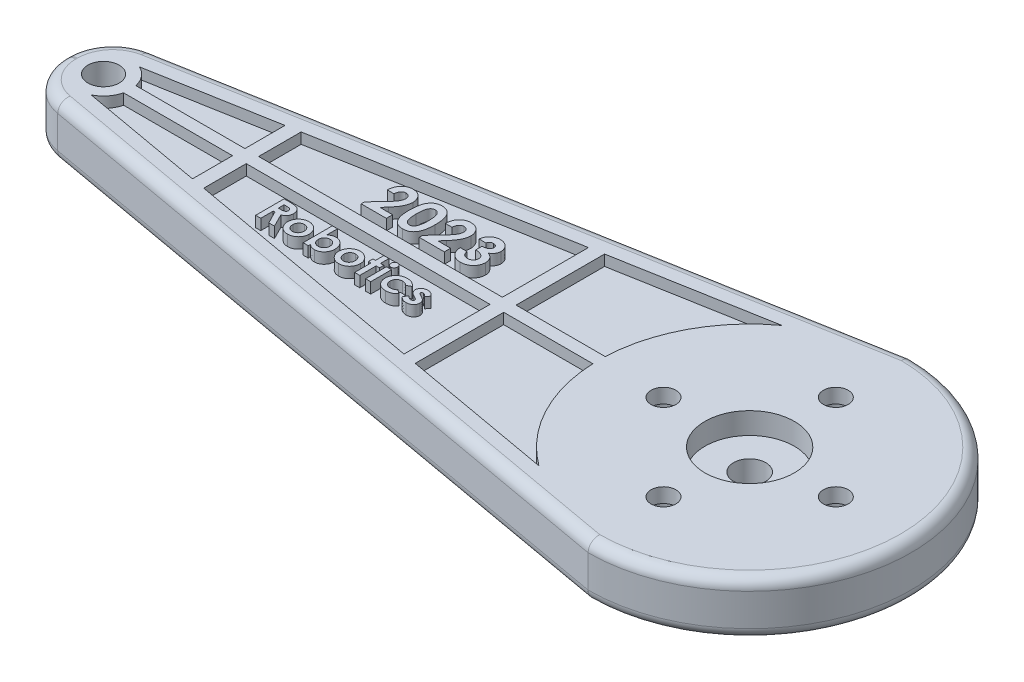
SolidWorks part; units mm, degrees
ref_plane "Front Plane" through (0, 0, 0) normal (0, 0, 1) x (1, 0, 0)
ref_plane "Top Plane" through (0, 0, 0) normal (0, 1, 0) x (1, 0, 0)
ref_plane "Right Plane" through (0, 0, 0) normal (1, 0, 0) x (0, 0, -1)
sketch "Sketch1" plane through (0, 0, 0) normal (0, 1, 0) x (1, 0, 0)
  line L1 (0, 0) -> (-63.5, 0)
  line L2 (0, 0) -> (0, 30)
  line L3 (0, 30) -> (-63.5, 30)
  line L4 (-63.5, 0) -> (-63.5, 30)
  dimension "D1" = 30
  dimension "D2" = 63.5
extrude "Boss-Extrude1" add sketch "Sketch1" along normal blind 5
sketch "Sketch2" plane through (0, 5, 0) normal (0, 1, 0) x (1, 0, 0)
  line L0 (0, 0) -> (0, 30) construction
  circle A0 centre (0, 15) radius 15
extrude "Boss-Extrude3" add sketch "Sketch2" against normal up to surface (5 mm away) up to face at (-31.75, 0, -15)
sketch "Sketch3" plane through (0, 5, 0) normal (0, 1, 0) x (1, 0, 0)
  circle A0 centre (0, 15) radius 1.5
  dimension "D1" = 3
extrude "Cut-Extrude1" cut sketch "Sketch3" against normal blind 5
sketch "Sketch5" plane through (0, 5, 0) normal (0, 1, 0) x (1, 0, 0)
  circle A0 centre (0, 15) radius 4.15
  dimension "D1" = 8.3
extrude "Cut-Extrude3" cut sketch "Sketch5" against normal blind 2
sketch "Sketch6" plane through (0, 0, 0) normal (0, -1, 0) x (1, 0, 0)
  circle A0 centre (0, -15) radius 8.001 construction
  circle A1 centre (0, -6.999) radius 1.15
  circle A2 centre (-8.001, -15) radius 1.15
  circle A3 centre (0, -23.001) radius 1.15
  circle A4 centre (8.001, -15) radius 1.15
  dimension "D1" = 16.002
  dimension "D2" = 2.3
  dimension "D3" = 2.3
  dimension "D4" = 2.3
  dimension "D5" = 2.3
extrude "Cut-Extrude4" cut sketch "Sketch6" against normal blind 5
sketch "Sketch7" plane through (0, 0, 0) normal (0, -1, 0) x (1, 0, 0)
  circle A0 centre (-8.001, -15) radius 2
  circle A1 centre (0, -6.999) radius 2
  circle A2 centre (0, -23.001) radius 2
  circle A3 centre (8.001, -15) radius 2
extrude "Cut-Extrude5" cut sketch "Sketch7" against normal blind 3.65
sketch "Sketch8" plane through (0, 0, 0) normal (0, -1, 0) x (1, 0, 0)
  circle A0 centre (-60, -15) radius 1.45
  circle A1 centre (0, -15) radius 1.5 construction
  dimension "D2" = 2.9
  dimension "D1" = 60
extrude "Cut-Extrude6" cut sketch "Sketch8" against normal blind 5
sketch "Sketch9" plane through (0, 0, 0) normal (0, -1, 0) x (1, 0, 0)
  line L0 (0, -30) -> (-63.5, -18.6666)
  line L1 (-63.5, -30) -> (-63.5, 0) construction
  line L2 (-63.5, -18.6666) -> (-63.5, -30)
  line L3 (-63.5, -30) -> (0, -30)
extrude "Cut-Extrude7" cut sketch "Sketch9" against normal blind 5
sketch "Sketch10" plane through (0, 0, 0) normal (0, -1, 0) x (1, 0, 0)
  line L0 (0, 0) -> (-63.5, -11.3334)
  line L1 (-63.5, -18.6666) -> (-63.5, 0) construction
  line L2 (-63.5, -11.3334) -> (-63.5, 0)
  line L3 (-63.5, 0) -> (0, 0)
extrude "Cut-Extrude8" cut sketch "Sketch10" against normal blind 5
fillet "Fillet1" radius 4.3 1 edges at (-63.5, 2.5, -18.6666)
fillet "Fillet2" radius 4.3 1 edges at (-63.5, 2.5, -11.3334)
fillet "Fillet3" radius 1 12 edges at (-63.5, 0, -15) (-63.5, 5, -15) (15, 0, -15) (-29.9778, 0, -5.3504) (-62.4969, 0, -17.8267) (-62.4969, 0, -12.1733) (-29.9778, 0, -24.6496) (-62.4969, 5, -17.8267) (-62.4969, 5, -12.1733) (-29.9778, 5, -5.3504) (15, 5, -15) (-29.9778, 5, -24.6496)
sketch "Sketch15" plane through (0, 5, 0) normal (0, 1, 0) x (1, 0, 0)
  line L1 (-8.2809, 3.7117) -> (-58.9087, 12.7508)
  line L4 (-8.2809, 26.2883) -> (-58.9087, 17.2492)
  arc A2 (-58.9087, 17.2492) -> (-58.9087, 12.7508) centre (-60, 15) cw
  arc A3 (-8.2809, 3.7117) -> (-8.2809, 26.2883) centre (0, 15) cw
extrude "Cut-Extrude11" cut sketch "Sketch15" against normal blind 1
sketch "Sketch17" plane through (0, 4, 0) normal (0, 1, 0) x (1, 0, 0)
  line L0 (-47.4458, 19.2958) -> (-47.4458, 10.7042)
  line L1 (-8.2809, 26.2883) -> (-58.9087, 17.2492) construction
  line L2 (-58.9087, 12.7508) -> (-8.2809, 3.7117) construction
  line L3 (-46.1731, 19.523) -> (-46.1731, 10.477)
  line L4 (-58.9087, 12.7508) -> (-8.2809, 3.7117) construction
  line L5 (-46.1731, 19.523) -> (-47.4458, 19.2958)
  line L6 (-47.4458, 10.7042) -> (-46.1731, 10.477)
extrude "Boss-Extrude4" add sketch "Sketch17" along normal blind 1
sketch "Sketch18" plane through (0, 4, 0) normal (0, 1, 0) x (1, 0, 0)
  line L0 (-22.2642, 23.7917) -> (-22.2642, 6.2083)
  line L1 (-8.2809, 26.2883) -> (-46.1731, 19.523) construction
  line L2 (-46.1731, 10.477) -> (-8.2809, 3.7117) construction
  line L3 (-22.2642, 6.2083) -> (-23.5331, 6.4348)
  line L4 (-46.1731, 10.477) -> (-8.2809, 3.7117) construction
  line L6 (-23.5331, 23.5652) -> (-22.2642, 23.7917)
  line L7 (-23.5331, 23.5652) -> (-23.5331, 6.4348)
extrude "Boss-Extrude5" add sketch "Sketch18" along normal blind 1
sketch "Sketch19" plane through (0, 4, 0) normal (0, 1, 0) x (1, 0, 0)
  line L7 (-57.5, 15.5751) -> (-47.4458, 15.5751)
  line L9 (-47.4458, 14.4249) -> (-57.5839, 14.4249)
  line L10 (-57.5839, 14.4249) -> (-57.5839, 15.5751)
  line L11 (-57.5839, 15.5751) -> (-57.5, 15.5751)
  line L12 (-13.9882, 15.5751) -> (-47.4458, 15.5751)
  line L13 (-47.4458, 14.4249) -> (-13.9882, 14.4249)
  line L15 (-13.9882, 14.4249) -> (-13.9007, 14.4249)
  line L16 (-13.9007, 14.4249) -> (-13.9007, 15.5751)
  line L17 (-13.9007, 15.5751) -> (-13.9882, 15.5751)
  arc A0 (-8.2809, 26.2883) -> (-8.2809, 3.7117) centre (0, 15) ccw construction
  arc A2 (-8.2809, 26.2883) -> (-8.2809, 3.7117) centre (0, 15) ccw construction
extrude "Boss-Extrude6" add sketch "Sketch19" along normal blind 1
sketch "Sketch20" plane through (0, 4, 0) normal (0, 1, 0) x (1, 0, 0)
  text T0 "<b>2023</b>"
  text T1 "<b>Robotics</b>" font "Century Gothic" height in points 10
  point P1 (-41.803, 16.4832)
  point P2 (-37.69, 16.5272)
  point P3 (0, 0)
  point P4 (0, 0)
  point P5 (0, 0)
  point P7 (-38.6404, 10.4465)
  point P8 (-41.9466, 10.8794)
  point P9 (-43.5997, 10.722)
  point P10 (0, 0)
extrude "Boss-Extrude10" add sketch "Sketch20" along normal blind 1
